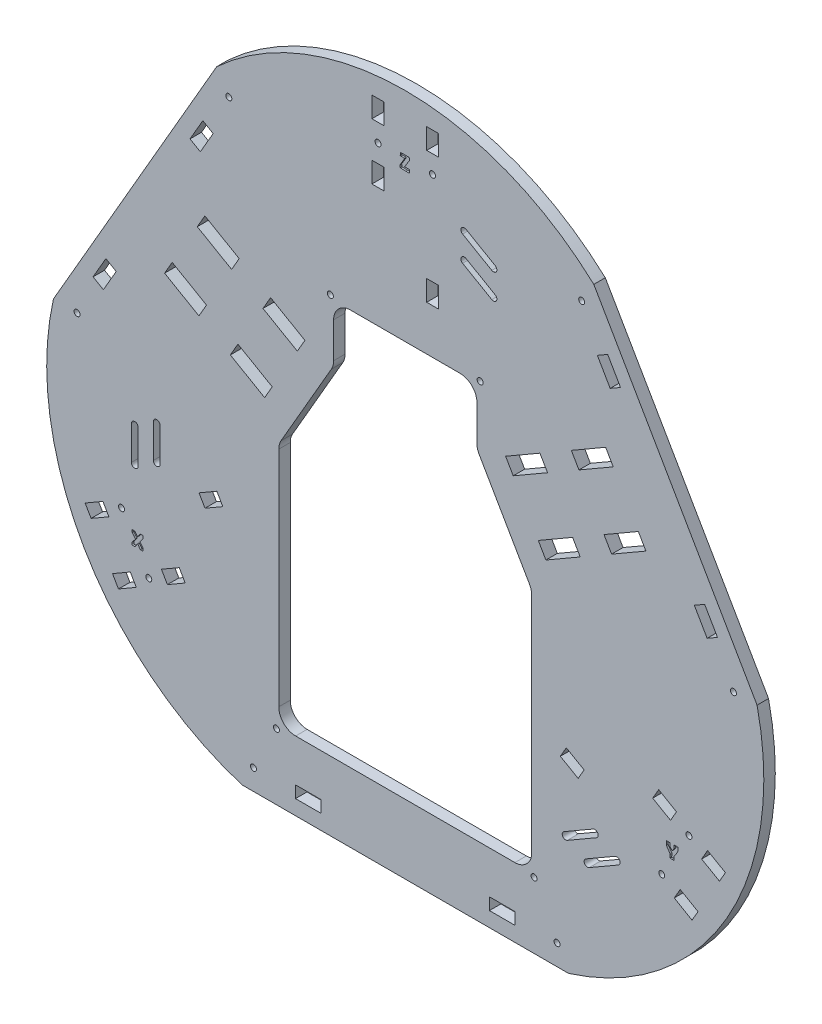
SolidWorks part; units mm, degrees
ref_plane "Front Plane" through (0, 0, 0) normal (0, 0, 1) x (1, 0, 0)
ref_plane "Top Plane" through (0, 0, 0) normal (0, 1, 0) x (1, 0, 0)
ref_plane "Right Plane" through (0, 0, 0) normal (1, 0, 0) x (0, 0, -1)
sketch "Sketch1" plane through (0, 0, 0) normal (0, 0, 1) x (1, 0, 0)
  line L0 (-96.8122, -185) -> (96.8122, -185)
  line L1 (208.6208, 8.6582) -> (111.8086, 176.3418)
  line L2 (-111.8086, 176.3418) -> (-208.6208, 8.6582)
  line L3 (0, 0) -> (-160.2147, 92.5) construction
  line L4 (0, 0) -> (160.2147, 92.5) construction
  line L5 (0, 0) -> (0, -185) construction
  arc A0 (-208.6208, 8.6582) -> (-96.8122, -185) centre (-47.6314, -27.5) ccw
  arc A1 (96.8122, -185) -> (208.6208, 8.6582) centre (47.6314, -27.5) ccw
  arc A2 (111.8086, 176.3418) -> (-111.8086, 176.3418) centre (0, 55) ccw
  circle A3 centre (0, 0) radius 3.5
  dimension "D1" = 165
  dimension "D6" = 7
  dimension "D2" = 193.6244
  dimension "D3" = 60
  dimension "D4" = 185
  dimension "D5" = 120
extrude "Boss-Extrude1" add sketch "Sketch1" along normal blind 6.8
sketch "Sketch2" plane through (0, 0, 6.8) normal (0, 0, 1) x (1, 0, 0)
  line L0 (0, 0) -> (0, -256.4096) construction
  line L1 (-65, -172.76) -> (-90, -172.76) construction
  line L2 (-65, -169.32) -> (-50, -169.32) construction
  line L3 (-65, -169.32) -> (-65, -176.2) construction
  line L4 (-65.1, -176.2) -> (-49.9, -176.2)
  line L5 (-50, -169.32) -> (-50, -176.2) construction
  line L6 (-96.8122, -185) -> (96.8122, -185) construction
  line L7 (50, -169.32) -> (50, -176.2) construction
  line L8 (65, -169.32) -> (65, -176.2) construction
  line L9 (65, -169.32) -> (50, -169.32) construction
  line L10 (65, -172.76) -> (90, -172.76) construction
  line L11 (65.1, -169.12) -> (49.9, -169.12)
  line L12 (-65.1, -169.12) -> (-65.1, -176.2)
  line L13 (-49.9, -169.12) -> (-49.9, -176.2)
  line L14 (-65.1, -169.12) -> (-49.9, -169.12)
  line L15 (-65, -169.12) -> (-50, -169.12) construction
  line L16 (-65.1, -169.32) -> (-65.1, -176.2) construction
  line L17 (-49.9, -169.32) -> (-49.9, -176.2) construction
  line L18 (49.9, -169.12) -> (49.9, -176.2)
  line L19 (65.1, -169.12) -> (65.1, -176.2)
  line L20 (65.1, -176.2) -> (49.9, -176.2)
  circle A0 centre (-90, -172.76) radius 1.775
  circle A1 centre (90, -172.76) radius 1.775
  dimension "D2" = 3.55
  dimension "D1" = 25
  dimension "D3" = 6.88
  dimension "D4" = 15
  dimension "D5" = 8.8
  dimension "D6" = 50
  dimension "D7" = 0.1
  dimension "D8" = 0.1
  dimension "D9" = 0.2
extrude "Cut-Extrude1" cut sketch "Sketch2" against normal blind 6.8
pattern_circular "CirPattern1" count 3 over 360 about axis through (0, 0, 6.8) along (0, 0, 1) of "Cut-Extrude1"
sketch "Sketch14" plane through (0, 0, 6.8) normal (0, 0, 1) x (1, 0, 0)
  line L0 (-16.14, 212.7) -> (-16.14, 157.2) construction
  line L1 (-12.7, 187.3) -> (12.7, 187.3) construction
  line L2 (-12.7, 187.3) -> (-12.7, 212.7) construction
  line L3 (-12.7, 212.7) -> (12.7, 212.7) construction
  line L4 (12.7, 187.3) -> (12.7, 212.7) construction
  line L5 (-12.7, 187.3) -> (12.7, 212.7) construction
  line L6 (-12.7, 212.7) -> (12.7, 187.3) construction
  line L7 (-19.58, 207.7) -> (-12.7, 207.7) construction
  line L8 (-19.58, 207.7) -> (-19.58, 195.7) construction
  line L9 (-19.58, 195.7) -> (-12.7, 195.7) construction
  line L10 (-12.7, 207.8) -> (-12.7, 195.6)
  line L11 (-19.58, 207.7) -> (-12.7, 195.7) construction
  line L12 (-19.58, 195.7) -> (-12.7, 207.7) construction
  line L13 (-16.14, 184.95) -> (-29.9314, 184.95) construction
  line L14 (-19.58, 174.2) -> (-12.7, 162.2) construction
  line L15 (-19.58, 162.2) -> (-12.7, 174.2) construction
  line L16 (-12.7, 162.1) -> (-12.7, 174.3)
  line L17 (-19.58, 174.2) -> (-12.7, 174.2) construction
  line L18 (-19.58, 162.2) -> (-19.58, 174.2) construction
  line L19 (-19.58, 162.2) -> (-12.7, 162.2) construction
  line L20 (0, 200) -> (0, 162.7) construction
  line L21 (19.58, 195.7) -> (12.7, 207.7) construction
  line L22 (19.58, 207.7) -> (12.7, 195.7) construction
  line L23 (12.7, 207.8) -> (12.7, 195.6)
  line L24 (19.58, 195.7) -> (12.7, 195.7) construction
  line L25 (19.58, 207.7) -> (19.58, 195.7) construction
  line L26 (19.58, 207.7) -> (12.7, 207.7) construction
  line L27 (16.14, 212.7) -> (16.14, 112.7) construction
  line L28 (16.14, 162.7) -> (46.1911, 162.7) construction
  line L29 (19.58, 117.7) -> (12.7, 129.7) construction
  line L30 (19.58, 129.7) -> (12.7, 117.7) construction
  line L31 (19.58, 117.7) -> (12.7, 117.7) construction
  line L32 (19.58, 117.7) -> (19.58, 129.7) construction
  line L33 (19.58, 129.7) -> (12.7, 129.7) construction
  line L34 (12.7, 117.6) -> (12.7, 129.8)
  line L35 (-19.78, 207.8) -> (-19.78, 195.6)
  line L36 (-19.78, 162.1) -> (-19.78, 174.3)
  line L37 (19.78, 207.8) -> (19.78, 195.6)
  line L38 (19.78, 117.6) -> (19.78, 129.8)
  line L39 (19.78, 117.6) -> (12.7, 117.6)
  line L40 (19.78, 129.8) -> (12.7, 129.8)
  line L41 (19.78, 195.6) -> (12.7, 195.6)
  line L42 (19.78, 207.8) -> (12.7, 207.8)
  line L43 (-19.78, 207.8) -> (-12.7, 207.8)
  line L44 (-19.78, 195.6) -> (-12.7, 195.6)
  line L45 (-19.78, 174.3) -> (-12.7, 174.3)
  line L46 (-19.78, 162.1) -> (-12.7, 162.1)
  line L47 (-19.58, 162.1) -> (-12.7, 162.1) construction
  line L48 (-19.78, 162.2) -> (-19.78, 174.2) construction
  line L49 (-19.58, 174.3) -> (-12.7, 174.3) construction
  line L50 (-19.58, 195.6) -> (-12.7, 195.6) construction
  line L51 (-19.78, 207.7) -> (-19.78, 195.7) construction
  line L52 (-19.58, 207.8) -> (-12.7, 207.8) construction
  line L53 (19.78, 207.7) -> (19.78, 195.7) construction
  line L54 (19.58, 207.8) -> (12.7, 207.8) construction
  line L55 (19.58, 195.6) -> (12.7, 195.6) construction
  line L56 (19.58, 129.8) -> (12.7, 129.8) construction
  line L57 (19.78, 117.7) -> (19.78, 129.7) construction
  line L58 (19.58, 117.6) -> (12.7, 117.6) construction
  circle A0 centre (-16.14, 184.95) radius 1.775
  circle A1 centre (16.14, 184.95) radius 1.775
  point P0 (0, 200)
  point P5 (-16.14, 201.7)
  point P19 (-16.14, 168.2)
  point P26 (16.14, 201.7)
  point P35 (16.14, 123.7)
  dimension "D8" = 3.55
  dimension "D9" = 0.2
  dimension "D1" = 200
  dimension "D2" = 25.4
  dimension "D3" = 6.88
  dimension "D4" = 12
  dimension "D5" = 5
  dimension "D6" = 55.5
  dimension "D7" = 100
  dimension "D10" = 0.2
  dimension "D11" = 0.2
  dimension "D12" = 0.2
  dimension "D13" = 0.1
  dimension "D14" = 0.1
  dimension "D15" = 0.1
  dimension "D16" = 0.1
  dimension "D17" = 0.1
  dimension "D18" = 0.1
  dimension "D19" = 0.1
  dimension "D20" = 0.1
extrude "Cut-Extrude12" cut sketch "Sketch14" against normal through all
pattern_circular "CirPattern2" count 3 over 360 about axis through (0, 0, 6.8) along (0, 0, -1) of "Cut-Extrude12"
sketch "Sketch8" plane through (0, 0, 6.8) normal (0, 0, 1) x (1, 0, 0)
  line L0 (-96.8122, -185) -> (96.8122, -185) construction
  line L1 (0, -47.3071) -> (-26.3556, -92.9563) construction
  line L2 (-26.3556, -92.9563) -> (26.3556, -92.9563) construction
  line L3 (26.3556, -92.9563) -> (0, -47.3071) construction
  line L12 (208.6208, 8.6582) -> (111.8086, 176.3418) construction
  line L13 (-111.8086, 176.3418) -> (-208.6208, 8.6582) construction
  line L14 (-31.1444, 6.6366) -> (0, -47.3071) construction
  line L15 (0, -47.3071) -> (31.1444, 6.6366) construction
  line L16 (88.6444, -92.9563) -> (26.3556, -92.9563) construction
  line L17 (26.3556, -92.9563) -> (57.5, -146.9) construction
  line L18 (-57.5, -146.9) -> (57.5, -146.9)
  line L19 (88.6444, -92.9563) -> (31.1444, 6.6366)
  line L20 (-31.1444, 6.6366) -> (-88.6444, -92.9563)
  line L21 (-57.5, -146.9) -> (-26.3556, -92.9563) construction
  line L22 (-26.3556, -92.9563) -> (-88.6444, -92.9563) construction
  arc A12 (-88.6444, -92.9563) -> (-57.5, -146.9) centre (-26.3556, -92.9563) ccw
  arc A13 (57.5, -146.9) -> (88.6444, -92.9563) centre (26.3556, -92.9563) ccw
  arc A14 (31.1444, 6.6366) -> (-31.1444, 6.6366) centre (0, -47.3071) ccw
  point P0 (0, -146.9)
  dimension "D4" = 115
  dimension "D1" = 38.1
sketch "Sketch9" plane through (0, 0, 6.8) normal (0, 0, 1) x (1, 0, 0)
  line L0 (-143.0529, -22.7748) -> (-115.0529, 25.7226)
  line L2 (-111.8086, 176.3418) -> (-208.6208, 8.6582) construction
  line L4 (-103.7945, 19.2226) -> (-131.7945, -29.2748)
  line L5 (-131.7945, -29.2748) -> (-143.0529, -22.7748)
  line L6 (-177.8397, 61.9726) -> (-63.3905, -4.1047) construction
  line L7 (-75.7945, 67.72) -> (-87.0529, 74.22)
  line L8 (-87.0529, 74.22) -> (-95.7079, 59.2291)
  line L10 (-103.7945, 19.2226) -> (-87.8895, 46.7709)
  line L11 (-175.0958, -4.2748) -> (-147.0958, 44.2226)
  line L13 (-156.6221, 49.7226) -> (-184.6221, 1.2252)
  line L14 (-184.6221, 1.2252) -> (-175.0958, -4.2748)
  line L15 (-128.6221, 98.22) -> (-119.0958, 92.72)
  line L16 (-156.6221, 49.7226) -> (-128.6221, 98.22)
  line L18 (-119.0958, 92.72) -> (-147.0958, 44.2226)
  line L30 (-150.6884, 87) -> (0, 0) construction
  line L32 (-87.8895, 46.7709) -> (-83.5594, 44.2709)
  line L33 (-83.5594, 44.2709) -> (-80.1194, 50.2291)
  line L34 (-80.1194, 50.2291) -> (-84.4495, 52.7291)
  line L35 (-95.7079, 59.2291) -> (-100.038, 61.7291)
  line L36 (-100.038, 61.7291) -> (-103.478, 55.7709)
  line L37 (-103.478, 55.7709) -> (-99.1479, 53.2709)
  line L38 (-99.1479, 53.2709) -> (-115.0529, 25.7226)
  line L39 (-84.4495, 52.7291) -> (-75.7945, 67.72)
  point P44 (-101.758, 58.75)
  dimension "D1" = 72.5
  dimension "D2" = 13
  dimension "D3" = 56
  dimension "D5" = 11
  dimension "D6" = 37
  dimension "D9" = 6.88
  dimension "D10" = 5
extrude "Cut-Extrude7" [suppressed] cut sketch "Sketch9" against normal through all
sketch "Sketch10" [suppressed] plane through (0, 0, 6.8) normal (0, 0, 1) x (1, 0, 0)
  line L0 (-129.2035, 51.213) -> (-144.2035, 25.2322) construction
  line L1 (-127.4714, 50.213) -> (-142.4714, 24.2322)
  line L2 (-130.9355, 52.213) -> (-145.9355, 26.2322)
  line L4 (-128.6221, 98.22) -> (-184.6221, 1.2252) construction
  line L5 (-159.5144, 68.713) -> (-174.5144, 42.7322) construction
  line L7 (-157.7823, 67.713) -> (-172.7823, 41.7322)
  line L8 (-161.2464, 69.713) -> (-176.2464, 43.7322)
  line L15 (-110.8414, 23.2911) -> (-156.6221, 49.7226) construction
  line L17 (-128.6221, 98.22) -> (-184.6221, 1.2252) construction
  line L18 (-175.0958, -4.2748) -> (-119.0958, 92.72) construction
  arc A0 (-127.4714, 50.213) -> (-130.9355, 52.213) centre (-129.2035, 51.213) ccw
  arc A1 (-145.9355, 26.2322) -> (-142.4714, 24.2322) centre (-144.2035, 25.2322) ccw
  arc A2 (-157.7823, 67.713) -> (-161.2464, 69.713) centre (-159.5144, 68.713) ccw
  arc A3 (-176.2464, 43.7322) -> (-172.7823, 41.7322) centre (-174.5144, 42.7322) ccw
  point P2 (-136.7035, 38.2226)
  point P7 (-167.0144, 55.7226)
  dimension "D4" = 2
  dimension "D1" = 12
  dimension "D2" = 12
  dimension "D3" = 30
extrude "Cut-Extrude8" [suppressed] cut sketch "Sketch10" against normal through all
fillet "Fillet3" [suppressed] radius 1.5
ref_plane "Plane1" [suppressed] through (0, 0, 0) normal (-0.5, -0.866, 0) x (-0.866, 0.5, 0)
sketch "Sketch12" plane through (0, 0, 6.8) normal (0, 0, 1) x (1, 0, 0)
  line L0 (-157.0666, -86.3821) -> (-155.7097, -86.3821)
  line L1 (-155.5363, -86.4884) -> (-155.5363, -87.9132)
  line L2 (159.3352, -87.8199) -> (159.4676, -87.8199)
  spline S0 degree 2 poles (-155.4424, -93.6089) (-155.4424, -94.1248) (-155.4759, -94.2311) knots 0 0 0 1 1 1
  spline S1 degree 2 poles (-155.4759, -94.2311) (-155.5587, -94.3523) (-155.8495, -94.3523) knots 0 0 0 1 1 1
  spline S2 degree 2 poles (-155.8495, -94.3523) (-155.9248, -94.3523) (-156.0795, -94.3523) knots 0 0 0 1 1 1
  spline S3 degree 2 poles (-156.0795, -94.3523) (-156.2723, -94.3486) (-156.506, -94.3486) (-156.9267, -94.3337) (-157.0417, -94.3337) knots 0 0 0 1 2 3 3 3
  spline S4 degree 2 poles (-157.0417, -94.3337) (-157.1456, -94.3337) (-158.6878, -92.1742) (-158.7077, -92.1705) knots 0 0 0 1 2 2 2
  spline S5 degree 2 poles (-158.7077, -92.1705) (-158.8301, -92.2768) (-159.5562, -93.3541) knots 0 0 0 1 1 1
  spline S6 degree 2 poles (-159.5562, -93.3541) (-160.2623, -94.3598) (-160.3393, -94.3821) knots 0 0 0 1 1 1
  spline S7 degree 2 poles (-160.3393, -94.3821) (-160.432, -94.4388) (-160.7795, -94.4388) knots 0 0 0 1 1 1
  spline S8 degree 2 poles (-160.7795, -94.4388) (-161.9014, -94.4388) (-161.9014, -94.1976) (-161.9618, -93.7388) (-161.9618, -93.6263) knots 0 0 0 1 2 3 3 3
  spline S9 degree 2 poles (-161.9618, -93.6263) (-161.9618, -92.9114) (-161.8642, -92.7877) knots 0 0 0 1 1 1
  spline S10 degree 2 poles (-161.8642, -92.7877) (-161.8604, -92.784) (-160.8796, -91.5483) knots 0 0 0 1 1 1
  spline S11 degree 2 poles (-160.8796, -91.5483) (-160.0621, -90.5538) (-160.0621, -90.3759) knots 0 0 0 1 1 1
  spline S12 degree 2 poles (-160.0621, -90.3759) (-160.0621, -90.241) (-160.8759, -89.2639) knots 0 0 0 1 1 1
  spline S13 degree 2 poles (-160.8759, -89.2639) (-161.3719, -88.6566) (-161.8642, -88.0468) knots 0 0 0 1 1 1
  spline S14 degree 2 poles (-161.8642, -88.0468) (-161.8977, -87.9579) (-161.9051, -87.8069) knots 0 0 0 1 1 1
  spline S15 degree 2 poles (-161.9051, -87.8069) (-161.9089, -87.6881) (-161.9051, -87.473) knots 0 0 0 1 1 1
  spline S16 degree 2 poles (-161.9051, -87.473) (-161.894, -87.2736) (-161.894, -87.2144) knots 0 0 0 1 1 1
  spline S17 degree 2 poles (-161.894, -87.2144) (-161.894, -87.0994) (-161.9618, -86.6675) (-161.9618, -86.5525) knots 0 0 0 1 2 2 2
  spline S18 degree 2 poles (-161.9618, -86.5525) (-161.9618, -86.4413) (-161.7504, -86.4413) knots 0 0 0 1 1 1
  spline S19 degree 2 poles (-161.7504, -86.4413) (-161.6267, -86.4413) (-161.1369, -86.4636) (-161.0169, -86.4636) knots 0 0 0 1 2 2 2
  spline S20 degree 2 poles (-161.0169, -86.4636) (-160.9032, -86.4636) (-160.4568, -86.4487) (-160.3885, -86.4487) knots 0 0 0 1 2 2 2
  spline S21 degree 2 poles (-160.3885, -86.4487) (-160.2847, -86.4487) (-158.7462, -88.6119) (-158.7226, -88.6119) knots 0 0 0 1 2 2 2
  spline S22 degree 2 poles (-158.7226, -88.6119) (-158.6063, -88.5254) (-157.8791, -87.4407) knots 0 0 0 1 1 1
  spline S23 degree 2 poles (-157.8791, -87.4407) (-157.1754, -86.3821) (-157.0666, -86.3821) knots 0 0 0 1 1 1
  spline S24 degree 2 poles (-155.7097, -86.3821) (-155.5363, -86.3821) (-155.5363, -86.4884) knots 0 0 0 1 1 1
  spline S25 degree 2 poles (-155.5363, -87.9132) (-155.5363, -88.0505) (-157.3681, -90.32) (-157.3681, -90.3647) knots 0 0 0 1 2 2 2
  spline S26 degree 2 poles (-157.3681, -90.3647) (-157.3681, -90.471) (-156.5346, -91.5247) knots 0 0 0 1 1 1
  spline S27 degree 2 poles (-156.5346, -91.5247) (-155.5636, -92.7368) (-155.5363, -92.7741) knots 0 0 0 1 1 1
  spline S28 degree 2 poles (-155.5363, -92.7741) (-155.4424, -92.894) (-155.4424, -93.6089) knots 0 0 0 1 1 1
  spline S29 degree 2 poles (161.606, -89.7978) (161.606, -90.0832) (161.5046, -90.2442) knots 0 0 0 1 1 1
  spline S30 degree 2 poles (161.5046, -90.2442) (160.7662, -91.7086) (159.4639, -93.3584) knots 0 0 0 1 1 1
  spline S31 degree 2 poles (159.4639, -93.3584) (159.3029, -93.5984) (159.3029, -93.7668) knots 0 0 0 1 1 1
  spline S32 degree 2 poles (159.3029, -93.7668) (159.3029, -94.0894) (159.4241, -95.2953) (159.4241, -95.5725) knots 0 0 0 1 2 2 2
  spline S33 degree 2 poles (159.4241, -95.5725) (159.4241, -95.6813) (159.3526, -95.6962) knots 0 0 0 1 1 1
  spline S34 degree 2 poles (159.3526, -95.6962) (159.3451, -95.6999) (159.2103, -95.7148) knots 0 0 0 1 1 1
  spline S35 degree 2 poles (159.2103, -95.7148) (158.9939, -95.7372) (158.1665, -95.7372) knots 0 0 0 1 1 1
  spline S36 degree 2 poles (158.1665, -95.7372) (157.3772, -95.7372) (157.1459, -95.7148) knots 0 0 0 1 1 1
  spline S37 degree 2 poles (157.1459, -95.7148) (156.9999, -95.6999) (156.9999, -95.5651) knots 0 0 0 1 1 1
  spline S38 degree 2 poles (156.9999, -95.5651) (156.9999, -95.2424) (157.1211, -94.0179) (157.1211, -93.7332) knots 0 0 0 1 2 2 2
  spline S39 degree 2 poles (157.1211, -93.7332) (157.1211, -93.5305) (156.9457, -93.3092) knots 0 0 0 1 1 1
  spline S40 degree 2 poles (156.9457, -93.3092) (156.2296, -92.3383) (154.948, -90.3567) knots 0 0 0 1 1 1
  spline S41 degree 2 poles (154.948, -90.3567) (154.8181, -90.1279) (154.8181, -89.993) knots 0 0 0 1 1 1
  spline S42 degree 2 poles (154.8181, -89.993) (154.8181, -89.6443) (154.8181, -88.2923) (154.8181, -87.9436) knots 0 0 0 1 2 2 2
  spline S43 degree 2 poles (154.8181, -87.9436) (154.8181, -87.7372) (154.8876, -87.7372) knots 0 0 0 1 1 1
  spline S44 degree 2 poles (154.8876, -87.7372) (155.2227, -87.7372) (156.5386, -87.8162) (156.8787, -87.8162) knots 0 0 0 1 2 2 2
  spline S45 degree 2 poles (156.8787, -87.8162) (156.9999, -87.8162) (156.9999, -87.9138) knots 0 0 0 1 1 1
  spline S46 degree 2 poles (156.9999, -87.9138) (156.9999, -88.1873) (156.9999, -89.3671) (156.9999, -89.6406) knots 0 0 0 1 2 2 2
  spline S47 degree 2 poles (156.9999, -89.6406) (156.9999, -89.7965) (157.5108, -90.5015) knots 0 0 0 1 1 1
  spline S48 degree 2 poles (157.5108, -90.5015) (157.9104, -91.0666) (158.212, -91.3438) knots 0 0 0 1 1 1
  spline S49 degree 2 poles (158.212, -91.3438) (158.4631, -91.0777) (158.8652, -90.5052) knots 0 0 0 1 1 1
  spline S50 degree 2 poles (158.8652, -90.5052) (159.4241, -89.8408) (159.4241, -89.6629) knots 0 0 0 1 1 1
  spline S51 degree 2 poles (159.4241, -89.6629) (159.4241, -89.3932) (159.3029, -88.2208) (159.3029, -87.9511) knots 0 0 0 1 2 2 2
  spline S52 degree 2 poles (159.3029, -87.9511) (159.3029, -87.8311) (159.3352, -87.8199) knots 0 0 0 1 1 1
  spline S53 degree 2 poles (159.4676, -87.8199) (159.8114, -87.8199) (161.1447, -87.7372) (161.4922, -87.7372) knots 0 0 0 1 2 2 2
  spline S54 degree 2 poles (161.4922, -87.7372) (161.606, -87.7372) (161.606, -88.0226) knots 0 0 0 1 1 1
  spline S55 degree 2 poles (161.606, -88.0226) (161.606, -88.3035) (161.606, -89.5132) (161.606, -89.7978) knots 0 0 0 1 2 2 2
  spline S56 degree 2 poles (2.2731, 178.6706) (1.9194, 178.6706) (0.5438, 178.7302) (0.1901, 178.7302) knots 0 0 0 1 2 2 2
  spline S57 degree 2 poles (0.1901, 178.7302) (-0.3022, 178.7302) (-2.2664, 178.7918) (-2.7587, 178.7918) knots 0 0 0 1 2 2 2
  spline S58 degree 2 poles (-2.7587, 178.7918) (-2.9812, 178.7918) (-3.0011, 178.918) knots 0 0 0 1 1 1
  spline S59 degree 2 poles (-3.0011, 178.918) (-3.0478, 179.2804) (-3.0925, 179.9547) knots 0 0 0 1 1 1
  spline S60 degree 2 poles (-3.0925, 179.9547) (-3.1223, 180.2612) (-3.1223, 180.2836) knots 0 0 0 1 1 1
  spline S61 degree 2 poles (-3.1223, 180.2836) (-3.1223, 180.3022) (-0.4147, 184.7436) (-0.4147, 184.8946) knots 0 0 0 1 2 2 2
  spline S62 degree 2 poles (-0.4147, 184.8946) (-0.4147, 184.9736) (-0.5508, 184.9736) knots 0 0 0 1 1 1
  spline S63 degree 2 poles (-0.5508, 184.9736) (-0.9293, 184.9736) (-2.4976, 184.9736) (-2.8799, 184.9736) knots 0 0 0 1 2 2 2
  spline S64 degree 2 poles (-2.8799, 184.9736) (-3.0011, 184.9736) (-3.0011, 185.0998) knots 0 0 0 1 1 1
  spline S65 degree 2 poles (-3.0011, 185.0998) (-3.0011, 185.2769) (-2.7587, 186.4766) (-2.7587, 186.7351) knots 0 0 0 1 2 2 2
  spline S66 degree 2 poles (-2.7587, 186.7351) (-2.7587, 186.8365) (-2.6151, 186.8365) knots 0 0 0 1 1 1
  spline S67 degree 2 poles (-2.6151, 186.8365) (-1.8407, 186.8365) (1.3836, 186.7918) (2.1581, 186.7918) knots 0 0 0 1 2 2 2
  spline S68 degree 2 poles (2.1581, 186.7918) (2.2793, 186.7918) (2.3434, 186.6214) knots 0 0 0 1 1 1
  spline S69 degree 2 poles (2.3434, 186.6214) (2.4535, 186.1969) (2.4535, 185.3447) knots 0 0 0 1 1 1
  spline S70 degree 2 poles (2.4535, 185.3447) (2.4535, 185.2334) (2.3459, 185.0468) knots 0 0 0 1 1 1
  spline S71 degree 2 poles (2.3459, 185.0468) (1.9922, 184.531) (0.8839, 182.7103) knots 0 0 0 1 1 1
  spline S72 degree 2 poles (0.8839, 182.7103) (-0.2594, 180.8793) (-0.3922, 180.5825) knots 0 0 0 0.883793 0.883793 0.883793
  spline S73 degree 2 poles (-0.3922, 180.5825) (-0.3671, 180.61) (-0.3059, 180.61) knots 0.410167 0.410167 0.410167 1 1 1
  spline S74 degree 2 poles (-0.3059, 180.61) (0.8099, 180.61) (1.4172, 180.6311) knots 0 0 0 1 1 1
  spline S75 degree 2 poles (1.4172, 180.6311) (1.5384, 180.6336) (1.9761, 180.6633) knots 0 0 0 1 1 1
  spline S76 degree 2 poles (1.9761, 180.6633) (2.2892, 180.7312) (2.482, 180.7312) knots 0 0 0 1 1 1
  spline S77 degree 2 poles (2.482, 180.7312) (2.5747, 180.7312) (2.5747, 180.6125) knots 0 0 0 1 1 1
  spline S78 degree 2 poles (2.5747, 180.6125) (2.5747, 179.68) (2.4535, 178.793) knots 0 0 0 1 1 1
  spline S79 degree 2 poles (2.4535, 178.793) (2.3968, 178.6706) (2.2731, 178.6706) knots 0 0 0 1 1 1
  point P91 (158.212, -91.3438)
extrude "Cut-Extrude10" cut sketch "Sketch12" against normal blind 1
sketch "Sketch15" plane through (0, 0, 6.8) normal (0, 0, 1) x (1, 0, 0)
  line L0 (-160.2147, 92.5) -> (-123.6674, 71.3994) construction
  line L1 (-111.8086, 176.3418) -> (-208.6208, 8.6582) construction
  circle A0 centre (-178.1184, 65.49) radius 4
  circle A1 centre (-145.7751, 121.51) radius 4
  dimension "D2" = 8
  dimension "D1" = 64.5
  dimension "D3" = 2
extrude "Cut-Extrude13" [suppressed] cut sketch "Sketch15" against normal through all
mirror "Mirror5" [suppressed] about plane through (0, 0, 0) normal (1, 0, 0)
fillet "Fillet4" [suppressed] radius 2
sketch "Sketch16" plane through (0, 0, 6.8) normal (0, 0, 1) x (1, 0, 0)
  line L0 (-75, 1) -> (-42.5, 57.2917)
  line L1 (75, 1) -> (-75, 1) construction
  line L2 (75, 1) -> (75, -144)
  line L3 (75, -144) -> (-75, -144)
  line L4 (-75, 1) -> (-75, -144)
  line L5 (75, 1) -> (-75, -144) construction
  line L6 (75, -144) -> (-75, 1) construction
  line L7 (-42.5, 91) -> (42.5, 91)
  line L8 (42.5, 57.2917) -> (75, 1)
  line L9 (-111.8086, 176.3418) -> (-208.6208, 8.6582) construction
  line L10 (-42.5, 57.2917) -> (-42.5, 91)
  line L12 (42.5, 57.2917) -> (42.5, 91)
  point P0 (0, -71.5)
  point P5 (0, 91)
  dimension "D1" = 150
  dimension "D2" = 145
  dimension "D3" = 1
  dimension "D4" = 90
  dimension "D5" = 85
extrude "Cut-Extrude14" cut sketch "Sketch16" against normal through all
sketch "Sketch17" plane through (0, 0, 6.8) normal (0, 0, 1) x (1, 0, 0)
  line L0 (0, 0) -> (0, -144) construction
  line L1 (76.4, -145.9) -> (-76.4, -145.9) construction
  line L2 (76.4, -145.9) -> (76.4, 1.9) construction
  line L3 (76.4, 1.9) -> (-76.4, 1.9) construction
  line L4 (-76.4, -145.9) -> (-76.4, 1.9) construction
  line L5 (76.4, -145.9) -> (-76.4, 1.9) construction
  line L6 (76.4, 1.9) -> (-76.4, -145.9) construction
  line L7 (-44.4, 92.9) -> (44.4, 92.9) construction
  line L8 (-75, -144) -> (75, -144) construction
  line L10 (42.5, 57.2917) -> (42.5, 91) construction
  line L11 (42.5, 91) -> (-42.5, 91) construction
  circle A0 centre (-76.4, 1.9) radius 1.775 construction
  circle A1 centre (76.4, 1.9) radius 1.775 construction
  circle A2 centre (76.4, -145.9) radius 1.775
  circle A3 centre (-76.4, -145.9) radius 1.775
  circle A4 centre (-44.4, 92.9) radius 1.775
  circle A5 centre (44.4, 92.9) radius 1.775
  point P0 (0, -72)
  point P12 (0, -72)
  point P17 (0, 92.9)
  dimension "D1" = 3.55
  dimension "D6" = 3.55
  dimension "D2" = 152.8
  dimension "D3" = 147.8
  dimension "D4" = 1.9
  dimension "D5" = 1.9
extrude "Cut-Extrude15" cut sketch "Sketch17" against normal through all
fillet "Fillet5" radius 10 8 edges at (-75, -144, 3.4) (75, -144, 3.4) (75, 1, 3.4) (-75, 1, 3.4) (-42.5, 91, 3.4) (42.5, 91, 3.4) (42.5, 57.2917, 3.4) (-42.5, 57.2917, 3.4)
sketch "Sketch19" plane through (0, 0, 6.8) normal (0, 0, 1) x (1, 0, 0)
  line L0 (-138.2073, 62.6179) -> (-142.7073, 54.8236)
  line L1 (-111.8086, 176.3418) -> (-208.6208, 8.6582) construction
  line L3 (-142.7073, 54.8236) -> (-122.3557, 43.0736)
  line L4 (-122.3557, 43.0736) -> (-117.8557, 50.8679)
  line L5 (-117.8557, 50.8679) -> (-138.2073, 62.6179)
  line L6 (-160.2147, 92.5) -> (-143.2371, 82.698) construction
  line L7 (-98.4807, 84.4264) -> (-102.9807, 76.6321)
  line L8 (-118.8323, 96.1764) -> (-98.4807, 84.4264)
  line L9 (-123.3323, 88.3821) -> (-118.8323, 96.1764)
  line L10 (-102.9807, 76.6321) -> (-123.3323, 88.3821)
  dimension "D1" = 34
  dimension "D2" = 9
  dimension "D3" = 23.5
  dimension "D4" = 29.75
extrude "Cut-Extrude16" cut sketch "Sketch19" against normal blind 12.5
pattern_linear "LPattern1" count 2 spacing 45 along (0.866, -0.5, 0) of "Cut-Extrude16"
sketch "Sketch21" plane through (0, 0, 6.8) normal (0, 0, 1) x (1, 0, 0)
  line L0 (52.3205, 155) -> (35, 165) construction
  line L1 (51.3205, 153.2679) -> (34, 163.2679)
  line L2 (53.3205, 156.7321) -> (36, 166.7321)
  line L3 (-19.78, 207.8) -> (-19.78, 195.6) construction
  arc A0 (51.3205, 153.2679) -> (53.3205, 156.7321) centre (52.3205, 155) ccw
  arc A1 (36, 166.7321) -> (34, 163.2679) centre (35, 165) ccw
  point P2 (43.6603, 160)
  dimension "D1" = 2
  dimension "D2" = 35
  dimension "D3" = 155
  dimension "D4" = 120
  dimension "D5" = 20
extrude "Cut-Extrude17" cut sketch "Sketch21" against normal blind 10
pattern_linear "LPattern2" count 2 spacing 15 along (0, -1, 0) of "Cut-Extrude17"
ref_axis "Axis1" through (0, 0, -0.34) along (0, 0, 1)
pattern_circular "CirPattern5" count 3 over 360 about axis through (0, 0, -0.34) along (0, 0, 1) of "LPattern2"
mirror "Mirror6" about plane through (0, 0, 0) normal (1, 0, 0) of "LPattern1"
